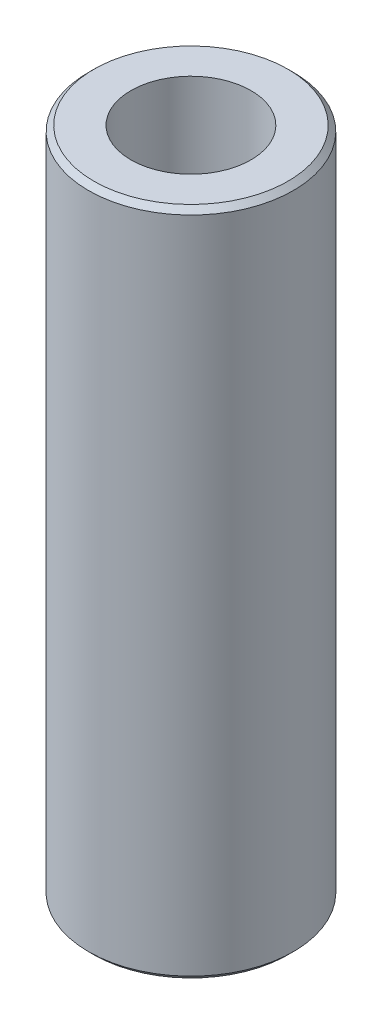
SolidWorks part; units mm, degrees
ref_plane "Front Plane" through (0, 0, 0) normal (0, 0, 1) x (1, 0, 0)
ref_plane "Top Plane" through (0, 0, 0) normal (0, 1, 0) x (1, 0, 0)
ref_plane "Right Plane" through (0, 0, 0) normal (1, 0, 0) x (0, 0, -1)
sketch "Sketch1" plane through (0, 0, 0) normal (0, 1, 0) x (1, 0, 0)
  circle A0 centre (0, 0) radius 45
  dimension "SHAFT_OD" = 90
extrude "Boss-Extrude1" add sketch "Sketch1" along normal blind 294.2973
sketch "Sketch2" plane through (0, 0, 0) normal (0, 1, 0) x (1, 0, 0)
  circle A0 centre (0, 0) radius 26.3869
  dimension "BORE_D" = 52.7738
extrude "Cut-Extrude1" cut sketch "Sketch2" along normal through all
chamfer "Chamfer1" distance 2.3625 angle 45 2 edges at (0, 294.2973, 45) (0, 0, 45)
